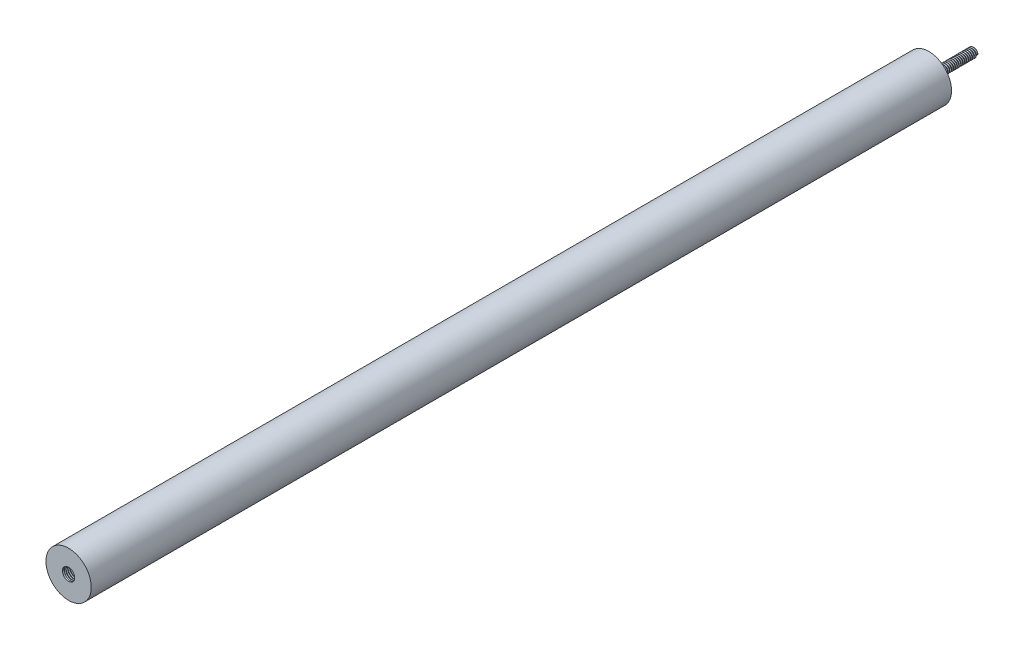
SolidWorks part; units mm, degrees
material "Cast Carbon Steel"
ref_plane "Front Plane" through (0, 0, 0) normal (0, 0, 1) x (1, 0, 0)
ref_plane "Top Plane" through (0, 0, 0) normal (0, 1, 0) x (1, 0, 0)
ref_plane "Right Plane" through (0, 0, 0) normal (1, 0, 0) x (0, 0, -1)
sketch "Sketch1" plane through (0, 0, 0) normal (0, 0, 1) x (1, 0, 0)
  line L1 (0, 0) -> (25.4, 0)
  line L2 (0, 0) -> (0, 32.766)
  line L3 (0, 32.766) -> (25.4, 32.766)
  line L4 (25.4, 0) -> (25.4, 32.766)
  dimension "D1" = 25.4
  dimension "D2" = 32.766
extrude "Boss-Extrude1" add sketch "Sketch1" against normal blind 482.6
sketch "Sketch2" plane through (0, 0, 0) normal (0, 0, 1) x (1, 0, 0)
  line L0 (25.4, 32.766) -> (0, 32.766) construction
  line L1 (25.4, 0) -> (25.4, 32.766) construction
  line L3 (0, 32.766) -> (25.4, 32.766)
  line L4 (0, 32.766) -> (0, 0)
  line L5 (0, 0) -> (25.4, 0)
  line L6 (25.4, 32.766) -> (25.4, 0)
  circle A0 centre (12.7, 16.383) radius 12.7
  line M2 (0, 32.766) -> (0, 0)
  line M3 (0, 0) -> (25.4, 0)
  line M4 (25.4, 0) -> (25.4, 32.766)
  line M5 (25.4, 32.766) -> (0, 32.766)
  dimension "D1" = 25.4
  dimension "D2" = 16.383
  dimension "D3" = 12.7
extrude "Cut-Extrude1" cut sketch "Sketch2" against normal through all contours A0 L6 M5 M2 | A0 L4 M3 M4 region at (12.7, 32.4637, 0) region at (12.7, 3.3807, 0)
sketch "Sketch3" plane through (0, 0, 0) normal (0, 0, 1) x (1, 0, 0)
  circle A0 centre (12.7, 16.383) radius 3.4544
  dimension "D1" = 6.9088
extrude "Cut-Extrude2" cut sketch "Sketch3" against normal blind 12.7
thread "Thread1" pitch 1.0583 method cut profile "Thread Profile1" start angle 0, offset 0, length 0, pitch 1.0583, diameter 6.9088
ref_plane "Plane1" through (9.2456, 16.383, 0) normal (0, -1, 0) x (-1, 0, 0)
sketch "Thread Profile1" plane through (9.2456, 16.383, 0) normal (0, -1, 0) x (-1, 0, 0)
  line L0 (0, 0) -> (0, 1.0583) construction
  line L1 (0, 0) -> (0.5728, 0.3307)
  line L2 (0.5728, 0.3307) -> (0.5728, 0.463)
  line L3 (0.5728, 0.463) -> (0, 0.7937)
  line L4 (0.5728, 0.3969) -> (0, 0.3969) construction
  line L11 (0, 0) -> (0, 0.7937)
  point P2 (0, 0)
  dimension "Pitch" = 1.0583
  dimension "Profile_Angle" = 60
  dimension "Profile_Land" = 0.1323
  dimension "Profile_Height" = 0.5728
sketch "Sketch4" plane through (0, 0, -482.6) normal (0, 0, -1) x (-1, 0, 0)
  circle A0 centre (-12.7, 16.383) radius 1.8986
  dimension "D1" = 3.7973
extrude "Boss-Extrude2" add sketch "Sketch4" along normal blind 25.4
thread "Thread2" pitch 1.0583 method extrude profile "Thread Profile2" start angle 0, offset 0, length 0, pitch 1.0583, diameter 3.7973
ref_plane "Plane2" through (14.5986, 16.383, -508) normal (0, -1, 0) x (1, 0, 0)
sketch "Thread Profile2" plane through (14.5986, 16.383, -508) normal (0, -1, 0) x (1, 0, 0)
  line L0 (0, 0) -> (0, 1.0583) construction
  line L1 (0, 0) -> (0.5728, 0.3307)
  line L2 (0.5728, 0.3307) -> (0.5728, 0.463)
  line L3 (0.5728, 0.463) -> (0, 0.7937)
  line L4 (0.5728, 0.3969) -> (0, 0.3969) construction
  line L11 (0, 0) -> (0, 0.7937)
  point P2 (0, 0)
  dimension "Pitch" = 1.0583
  dimension "Profile_Angle" = 60
  dimension "Profile_Land" = 0.1323
  dimension "Profile_Height" = 0.5728
